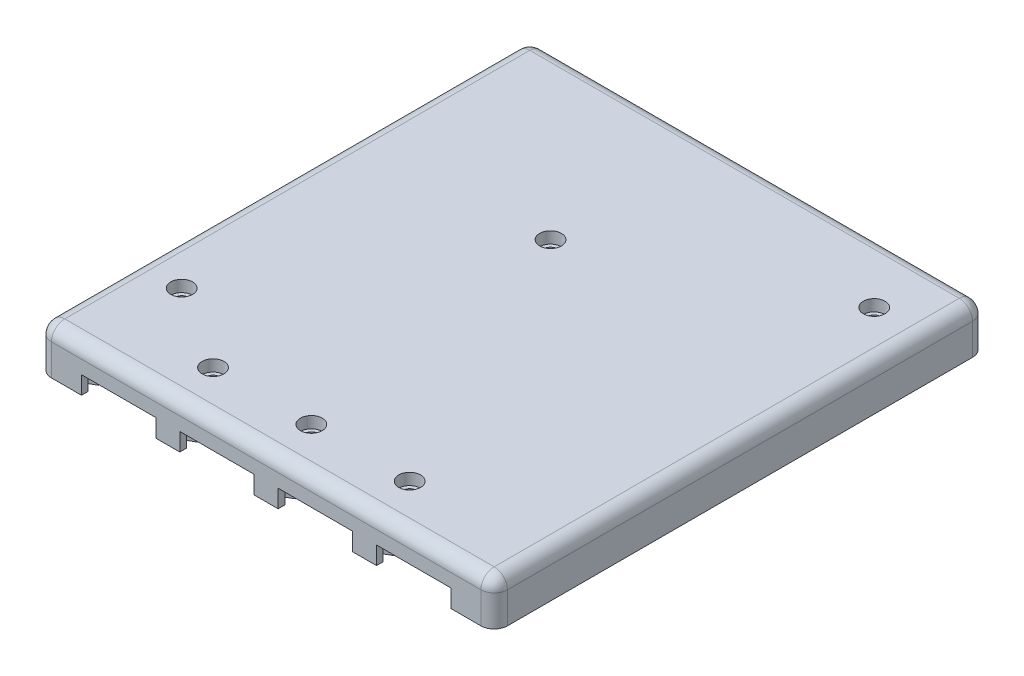
SolidWorks part; units mm, degrees
ref_plane "Front Plane" through (0, 0, 0) normal (0, 0, 1) x (1, 0, 0)
ref_plane "Top Plane" through (0, 0, 0) normal (0, 1, 0) x (1, 0, 0)
ref_plane "Right Plane" through (0, 0, 0) normal (1, 0, 0) x (0, 0, -1)
sketch "Sketch1" plane through (0, 0, 0) normal (0, 1, 0) x (1, 0, 0)
  line L0 (-1, -1) -> (-1, 15.7637) construction
  line L1 (-6, -6) -> (79.8, -6)
  line L2 (-6, -6) -> (-6, 86.5)
  line L3 (-6, 86.5) -> (79.8, 86.5)
  line L4 (79.8, -6) -> (79.8, 86.5)
  line L5 (-1, -1) -> (16.6536, -1) construction
  circle A0 centre (2.5, 12.5) radius 2.05
  circle A1 centre (18.4, 2.5) radius 2.05
  circle A2 centre (36.9, 2.5) radius 2.05
  circle A3 centre (55.4, 2.5) radius 2.05
  circle A4 centre (29.3, 55.1) radius 2.05
  circle A5 centre (70.8, 74.5) radius 2.05
  dimension "D16" = 4.1
  dimension "D1" = 92.5
  dimension "D2" = 85.8
  dimension "D3" = 5
  dimension "D4" = 1
  dimension "D5" = 1
  dimension "D6" = 5
  dimension "D7" = 12.5
  dimension "D8" = 2.5
  dimension "D9" = 18.4
  dimension "D10" = 18.5
  dimension "D11" = 18.5
  dimension "D12" = 55.1
  dimension "D13" = 29.3
  dimension "D14" = 41.5
  dimension "D15" = 74.5
  dimension "D17" = 2.5
extrude "Boss-Extrude1" add sketch "Sketch1" along normal blind 3.175
sketch "Sketch2" plane through (0, 0, 0) normal (0, 1, 0) x (1, 0, 0)
  line L0 (2.5, 7.5) -> (-1, 7.5)
  line L1 (-6, 86.5) -> (79.8, 86.5)
  line L2 (-6, 86.5) -> (-6, -6)
  line L3 (-6, -6) -> (79.8, -6)
  line L4 (79.8, 86.5) -> (79.8, -6)
  line L5 (-1, 7.5) -> (-1, -1)
  line L6 (-1, -1) -> (13.4, -1)
  line L7 (13.4, -1) -> (13.4, 2.5)
  line L8 (2.5, 17.5) -> (-1, 17.5)
  line L9 (-1, 17.5) -> (-1, 81.5)
  line L10 (-1, 81.5) -> (65.8, 81.5)
  line L11 (65.8, 74.5) -> (65.8, 81.5)
  line L13 (70.8, 69.5) -> (74.8, 69.5)
  line L14 (74.8, 69.5) -> (74.8, -1)
  line L15 (74.8, -1) -> (60.4, -1)
  line L16 (60.4, -1) -> (60.4, 2.5)
  line L17 (23.4, 2.5) -> (23.4, -1)
  line L18 (23.4, -1) -> (31.9, -1)
  line L19 (31.9, -1) -> (31.9, 2.5)
  line L20 (41.9, 2.5) -> (41.9, -1)
  line L21 (41.9, -1) -> (50.4, -1)
  line L22 (50.4, -1) -> (50.4, 2.5)
  circle A0 centre (2.5, 12.5) radius 1.35
  circle A1 centre (18.4, 2.5) radius 1.35
  circle A2 centre (36.9, 2.5) radius 1.35
  circle A3 centre (55.4, 2.5) radius 1.35
  circle A4 centre (29.3, 55.1) radius 1.35
  circle A5 centre (70.8, 74.5) radius 1.35
  circle A6 centre (29.3, 55.1) radius 3.35
  arc A7 (2.5, 17.5) -> (2.5, 7.5) centre (2.5, 12.5) cw
  arc A8 (13.4, 2.5) -> (23.4, 2.5) centre (18.4, 2.5) cw
  arc A9 (31.9, 2.5) -> (41.9, 2.5) centre (36.9, 2.5) cw
  arc A10 (50.4, 2.5) -> (60.4, 2.5) centre (55.4, 2.5) cw
  arc A11 (65.8, 74.5) -> (70.8, 69.5) centre (70.8, 74.5) ccw
  dimension "D1" = 2.7
  dimension "D2" = 6.7
  dimension "D3" = 5
  dimension "D4" = 5
  dimension "D5" = 5
  dimension "D6" = 5
  dimension "D7" = 5
extrude "Boss-Extrude2" add sketch "Sketch2" against normal blind 1.905 contours L4 L1 L2 L3 A0 A1 A2 A3 A5 L11 A11 L13 L14 L15 L16 A10 L22 L21 L20 A9 L19 L18 L17 A8 L7 L6 L5 L0 A7 L8 L9 L10 | A6 A4 region at (36.9, 0, -85.2383) region at (26.0448, 0, -55.1)
extrude "Boss-Extrude3" add sketch "Sketch2<3>" along normal blind 1 contours L4 L1 L2 L3 A0 A1 A2 A3 A5 L11 A11 L13 L14 L15 L16 A10 L22 L21 L20 A9 L19 L18 L17 A8 L7 L6 L5 L0 A7 L8 L9 L10 | A6 A4 region at (36.9, 0, -85.2383) region at (26.0448, 0, -55.1)
sketch "Sketch2<3>" plane through (0, 0, 0) normal (0, 1, 0) x (1, 0, 0) same geometry as "Sketch2"
ref_plane "Plane1" through (0, -1.905, 0) normal (0, -1, 0) x (-1, 0, 0)
sketch "Sketch3" plane through (0, -1.905, 0) normal (0, -1, 0) x (-1, 0, 0)
  line L1 (6, 86.5) -> (-79.8, 86.5)
  line L2 (6, 86.5) -> (6, -6)
  line L3 (6, -6) -> (-79.8, -6)
  line L4 (-79.8, 86.5) -> (-79.8, -6)
  line L5 (1, 81.5) -> (-74.8, 81.5)
  line L6 (1, 81.5) -> (1, -1)
  line L7 (1, -1) -> (-74.8, -1)
  line L8 (-74.8, 81.5) -> (-74.8, -1)
  dimension "D1" = 5
  dimension "D2" = 5
  dimension "D3" = 5
  dimension "D4" = 5
extrude "Boss-Extrude4" add sketch "Sketch3" along normal blind 3.3
sketch "Sketch4" plane through (0, 0, 0) normal (0, 0, 1) x (1, 0, 0)
  line L0 (79.8, -5.205) -> (-6, -5.205) construction
  line L1 (2.15, -1.845) -> (16.15, -1.845)
  line L2 (2.15, -1.845) -> (2.15, -8.595)
  line L3 (2.15, -8.595) -> (16.15, -8.595)
  line L4 (16.15, -1.845) -> (16.15, -8.595)
  line L5 (20.65, -1.845) -> (34.65, -1.845)
  line L6 (20.65, -1.845) -> (20.65, -8.595)
  line L7 (20.65, -8.595) -> (34.65, -8.595)
  line L8 (34.65, -1.845) -> (34.65, -8.595)
  line L9 (39.15, -1.845) -> (53.15, -1.845)
  line L10 (39.15, -1.845) -> (39.15, -8.595)
  line L11 (39.15, -8.595) -> (53.15, -8.595)
  line L12 (53.15, -1.845) -> (53.15, -8.595)
  line L13 (57.65, -1.845) -> (71.65, -1.845)
  line L14 (57.65, -1.845) -> (57.65, -8.595)
  line L15 (57.65, -8.595) -> (71.65, -8.595)
  line L16 (71.65, -1.845) -> (71.65, -8.595)
  point P16 (9.15, -1.845)
  point P17 (27.65, -1.845)
  point P18 (46.15, -1.845)
  point P19 (64.65, -1.845)
  dimension "D1" = 14
  dimension "D2" = 14
  dimension "D3" = 14
  dimension "D4" = 14
  dimension "D5" = 9.15
  dimension "D6" = 18.5
  dimension "D7" = 18.5
  dimension "D8" = 18.5
  dimension "D9" = 6.75
  dimension "D10" = 3.36
extrude "Cut-Extrude1" cut sketch "Sketch4" along normal through all
sketch "Sketch5" plane through (0, 0, 0) normal (0, 0, 1) x (1, 0, 0)
  line L0 (-1, -5.205) -> (74.8, -5.205) construction
  line L1 (53, -3.205) -> (63, -3.205)
  line L2 (53, -3.205) -> (53, -9.205)
  line L3 (53, -9.205) -> (63, -9.205)
  line L4 (63, -3.205) -> (63, -9.205)
  point P4 (58, -3.205)
  dimension "D1" = 58
  dimension "D2" = 10
  dimension "D3" = 6
  dimension "D4" = 2
extrude "Cut-Extrude2" cut sketch "Sketch5" against normal through all
ref_plane "Plane2" through (-6, 0, 0) normal (-1, 0, 0) x (0, 0, 1)
sketch "Sketch6" plane through (-6, 0, 0) normal (-1, 0, 0) x (0, 0, 1)
  line L0 (-59.6, 0) -> (-59.6, -8.95)
  line L1 (-59.6, 0) -> (-50.6, 0)
  line L2 (-59.6, -8.95) -> (-59.1311, -8.95)
  line L3 (-50.6, 0) -> (-50.6, -8.95)
  line L4 (-50.6, -8.95) -> (-51.0689, -8.95)
  arc A0 (-59.1311, -8.95) -> (-51.0689, -8.95) centre (-55.1, -10.95) cw
  point P3 (-55.1, 0)
  dimension "D1" = 4.5
  dimension "D2" = 10.95
  dimension "D3" = 55.1
  dimension "D4" = 9
  dimension "D5" = 2
extrude "Boss-Extrude5" add sketch "Sketch6" against normal blind 3.5
fillet "Fillet1" radius 2.5 1 edges at (79.8, -1.015, 6)
fillet "Fillet2" radius 2.5 1 edges at (79.8, -1.015, -86.5)
fillet "Fillet3" radius 2.5 1 edges at (-6, -1.015, -86.5)
fillet "Fillet4" radius 2.5 1 edges at (-6, -1.015, 6)
fillet "Fillet5" radius 2.5 8 edges at (79.0678, 3.175, -85.7678) (79.8, 3.175, -40.25) (79.0678, 3.175, 5.2678) (36.9, 3.175, 6) (-5.2678, 3.175, 5.2678) (-6, 3.175, -40.25) (-5.2678, 3.175, -85.7678) (36.9, 3.175, -86.5)
ref_plane "Plane3" through (0, -5.205, 0) normal (0, -1, 0) x (-1, 0, 0)
sketch "Sketch7" plane through (0, -5.205, 0) normal (0, -1, 0) x (-1, 0, 0)
  line L0 (-2.15, -3.75) -> (-0.4, -3.75) construction
  line L2 (-2.15, -2.75) -> (-0.4, -3.75)
  line L3 (-2.15, -6) -> (-2.15, -1) construction
  line L4 (-0.4, -3.75) -> (-2.15, -4.75)
  line L5 (-2.15, -4.75) -> (-2.15, -2.75)
  line L6 (-16.15, -2.75) -> (-17.9, -3.75)
  line L7 (-16.15, -1) -> (-16.15, -6) construction
  line L8 (-17.9, -3.75) -> (-16.15, -4.75)
  line L9 (-16.15, -4.75) -> (-16.15, -2.75)
  line L10 (-20.65, -2.75) -> (-18.9, -3.75)
  line L11 (-20.65, -6) -> (-20.65, 0) construction
  line L12 (-18.9, -3.75) -> (-20.65, -4.75)
  line L13 (-20.65, -6) -> (-20.65, -1) construction
  line L14 (-20.65, -4.75) -> (-20.65, -2.75)
  line L15 (-34.65, -2.75) -> (-36.4, -3.75)
  line L16 (-34.65, -6) -> (-34.65, 0) construction
  line L17 (-36.4, -3.75) -> (-34.65, -4.75)
  line L18 (-34.65, -1) -> (-34.65, -6) construction
  line L19 (-34.65, -4.75) -> (-34.65, -2.75)
  line L20 (-39.15, -2.75) -> (-39.15, -4.75)
  line L21 (-39.15, -6) -> (-39.15, 0) construction
  line L22 (-39.15, -4.75) -> (-37.4, -3.75)
  line L23 (-37.4, -3.75) -> (-39.15, -2.75)
  line L24 (-53.15, -2.75) -> (-53.15, -4.75)
  line L25 (-53.15, -1) -> (-53.15, -6) construction
  line L26 (-53.15, -4.75) -> (-54.9, -3.75)
  line L27 (-54.9, -3.75) -> (-53.15, -2.75)
  line L28 (-57.65, -4.75) -> (-55.9, -3.75)
  line L29 (-57.65, -6) -> (-57.65, -1) construction
  line L30 (-55.9, -3.75) -> (-57.65, -2.75)
  line L31 (-57.65, -2.75) -> (-57.65, -4.75)
  line L32 (-71.65, -2.75) -> (-73.4, -3.75)
  line L33 (-71.65, -6) -> (-71.65, -1) construction
  line L34 (-73.4, -3.75) -> (-71.65, -4.75)
  line L35 (-71.65, -4.75) -> (-71.65, -2.75)
  dimension "D1" = 1.75
  dimension "D2" = 2
  dimension "D3" = 1.75
  dimension "D4" = 1.75
  dimension "D5" = 1.75
  dimension "D6" = 1.75
  dimension "D7" = 1.75
  dimension "D8" = 1.75
  dimension "D9" = 1.75
  dimension "D10" = 3.75
extrude "Cut-Extrude3" cut sketch "Sketch7" against normal blind 3.36
sketch "Sketch8" plane through (0, 0, 0) normal (1, 0, 0) x (0, 0, -1)
  line L0 (-4.75, -1.9) -> (-2.75, -1.9)
  line L1 (-2.75, -1.9) -> (-3.75, -0.15)
  line L2 (-3.75, -0.15) -> (-4.75, -1.9)
  line L3 (-3.75, -1.9) -> (-3.75, -0.15) construction
  dimension "D1" = 1.75
  dimension "D2" = 2
  dimension "D3" = 1.9
  dimension "D4" = 3.75
extrude "Cut-Extrude4" cut sketch "Sketch8" along normal blind 75
ref_plane "Plane4" through (0, 0, 6) normal (0, 0, 1) x (1, 0, 0)
sketch "Sketch10" plane through (0, 0, 6) normal (0, 0, 1) x (1, 0, 0)
  line L1 (2.15, -1.845) -> (-2.351, -1.845)
  line L2 (2.15, -1.845) -> (2.15, 0.155)
  line L3 (2.15, 0.155) -> (-2.351, 0.155)
  line L4 (-2.351, -1.845) -> (-2.351, 0.155)
  line L5 (20.65, -1.845) -> (16.149, -1.845)
  line L6 (20.65, -1.845) -> (20.65, 0.155)
  line L7 (20.65, 0.155) -> (16.149, 0.155)
  line L8 (16.149, -1.845) -> (16.149, 0.155)
  line L9 (39.15, -1.845) -> (34.649, -1.845)
  line L10 (39.15, -1.845) -> (39.15, 0.155)
  line L11 (39.15, 0.155) -> (34.649, 0.155)
  line L12 (34.649, -1.845) -> (34.649, 0.155)
  line L13 (57.65, -1.845) -> (53.149, -1.845)
  line L14 (57.65, -1.845) -> (57.65, 0.155)
  line L15 (57.65, 0.155) -> (53.149, 0.155)
  line L16 (53.149, -1.845) -> (53.149, 0.155)
  line L17 (71.65, -1.845) -> (76.151, -1.845)
  line L18 (71.65, -1.845) -> (71.65, 0.155)
  line L19 (71.65, 0.155) -> (76.151, 0.155)
  line L20 (76.151, -1.845) -> (76.151, 0.155)
  dimension "D1" = 2
  dimension "D2" = 4.501
extrude "Boss-Extrude6" add sketch "Sketch10" against normal blind 5
sketch "Sketch13" plane through (0, 0, 0) normal (1, 0, 0) x (0, 0, -1)
  circle A0 centre (55.1, -10.95) radius 6.35
  dimension "D1" = 12.7
  dimension "D2" = 55.1
  dimension "D3" = 10.95
extrude "Cut-Extrude5" cut sketch "Sketch13" against normal blind 2.5
